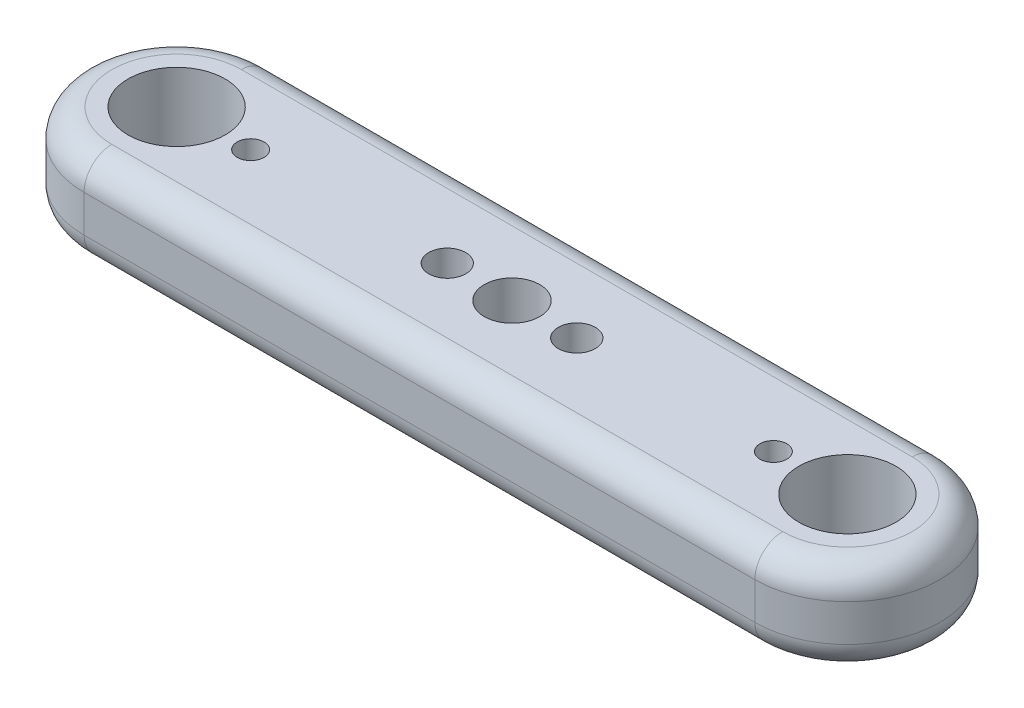
SolidWorks part; units mm, degrees
ref_plane "Front Plane" through (0, 0, 0) normal (0, 0, 1) x (1, 0, 0)
ref_plane "Top Plane" through (0, 0, 0) normal (0, 1, 0) x (1, 0, 0)
ref_plane "Right Plane" through (0, 0, 0) normal (1, 0, 0) x (0, 0, -1)
sketch "Sketch2" plane through (0, 0, 0) normal (0, 1, 0) x (1, 0, 0)
  line L4 (-36.25, 10) -> (36.25, 10)
  line L10 (36.25, -10) -> (-36.25, -10)
  arc A1 (0, -5) -> (0, 5) centre (0, 0) ccw
  circle A5 centre (0, 0) radius 5
  circle A6 centre (-36.25, 0) radius 5
  circle A7 centre (36.25, 0) radius 5
  arc A8 (-36.25, 10) -> (-36.25, -10) centre (-36.25, 0) ccw
  arc A9 (36.25, -10) -> (36.25, 10) centre (36.25, 0) ccw
  circle A10 centre (-36.25, 0) radius 10 construction
  circle A11 centre (36.25, 0) radius 10 construction
  point P3 (-19.375, 0)
  dimension "D1" = 5
  dimension "D2" = 5
extrude "Boss-Extrude1" add sketch "Sketch2" along normal blind 10 contours L10 A9 L4 A8 A5 A1 A6 A7 region at (0, 0, -9.0536)
fillet "Fillet1" radius 3 8 edges at (-46.25, 0, 0) (0, 0, 10) (46.25, 0, 0) (-46.25, 10, 0) (0, 10, 10) (46.25, 10, 0) (0, 0, -10) (0, 10, -10)
sketch "Sketch3" plane through (0, 10, 0) normal (0, 1, 0) x (1, 0, 0)
  line L0 (0, 0) -> (-6.5, 0)
  line L1 (-6.5, 0) -> (7.6495, 0)
  circle A0 centre (0, 0) radius 5
  circle M5 centre (0, 0) radius 5
extrude "Boss-Extrude2" add sketch "Sketch3" against normal blind 10 contours L0 L1 M5 | L1 L0 M5 region at (0, 10, 2.1221) region at (0, 10, -2.1221)
sketch "Sketch4" plane through (0, 10, 0) normal (0, 1, 0) x (1, 0, 0)
  line L0 (0, 0) -> (-8.2, 0)
  line L1 (0, 0) -> (8.2, 0)
  circle A0 centre (-8.2, 0) radius 1.5
  circle A1 centre (8.2, 0) radius 1.5
sketch "Sketch5" plane through (0, 10, 0) normal (0, 1, 0) x (1, 0, 0)
  circle A0 centre (-36.25, 0) radius 4.5
  circle A1 centre (-36.25, 0) radius 5
  circle A2 centre (36.25, 0) radius 5
  circle A3 centre (36.25, 0) radius 4.5
extrude "Boss-Extrude3" add sketch "Sketch5" against normal up to surface (10 mm away) up to face at (0, 0, 0)
sketch "Sketch6" plane through (0, 10, 0) normal (0, 1, 0) x (1, 0, 0)
  line L0 (7, 0) -> (-7, 0)
  circle A1 centre (-7, 0) radius 2
  circle A2 centre (7, 0) radius 2
extrude "Cut-Extrude1" cut sketch "Sketch6" against normal blind 10 contours A1 | A2 region at (-8.9434, 10, 0) region at (7, 10, -1.9434)
sketch "Sketch7" plane through (0, 10, 0) normal (0, 1, 0) x (1, 0, 0)
  circle A0 centre (0, 0) radius 3
extrude "Cut-Extrude2" cut sketch "Sketch7" against normal blind 10
sketch "Sketch8" plane through (0, 10, 0) normal (0, 1, 0) x (1, 0, 0)
  circle A0 centre (-36.25, 0) radius 4.65
  circle A1 centre (36.25, 0) radius 4.65
extrude "Cut-Extrude3" cut sketch "Sketch8" against normal blind 17
sketch "Sketch9" plane through (0, 10, 0) normal (0, 1, 0) x (1, 0, 0)
  circle A0 centre (-36.25, 0) radius 5.25
  circle A1 centre (36.25, 0) radius 5.25
  circle A2 centre (-36.25, 0) radius 8
  circle A3 centre (36.25, 0) radius 8
  circle A4 centre (-28.25, 0) radius 1.45
  circle A5 centre (28.25, 0) radius 1.45
  circle M1 centre (-36.25, 0) radius 4.65
  circle M2 centre (36.25, 0) radius 4.65
extrude "Cut-Extrude4" cut sketch "Sketch9" against normal blind 10 contours M1 | M2 | A0 M1 | A1 M2 region at (-41.3515, 10, 0) region at (31.1485, 10, 0) region at (-36.25, 10, 0) region at (36.25, 10, 0)
extrude "Cut-Extrude5" cut sketch "Sketch9<3>" against normal blind 10 contours A2 A4 | A2 A4 | A3 A5 | A3 A5 region at (-28.8885, 10, 0) region at (-27.6589, 10, 0) region at (28.8885, 10, 0) region at (27.6589, 10, 0)
sketch "Sketch9<3>" plane through (0, 10, 0) normal (0, 1, 0) x (1, 0, 0) same geometry as "Sketch9"
sketch "Sketch10" plane through (0, 10, 0) normal (0, 1, 0) x (1, 0, 0)
  circle A0 centre (-36.25, 0) radius 5.25
  circle A1 centre (-36.25, 0) radius 6.5
  circle A2 centre (36.25, 0) radius 5.25
  circle A3 centre (36.25, 0) radius 6.5
